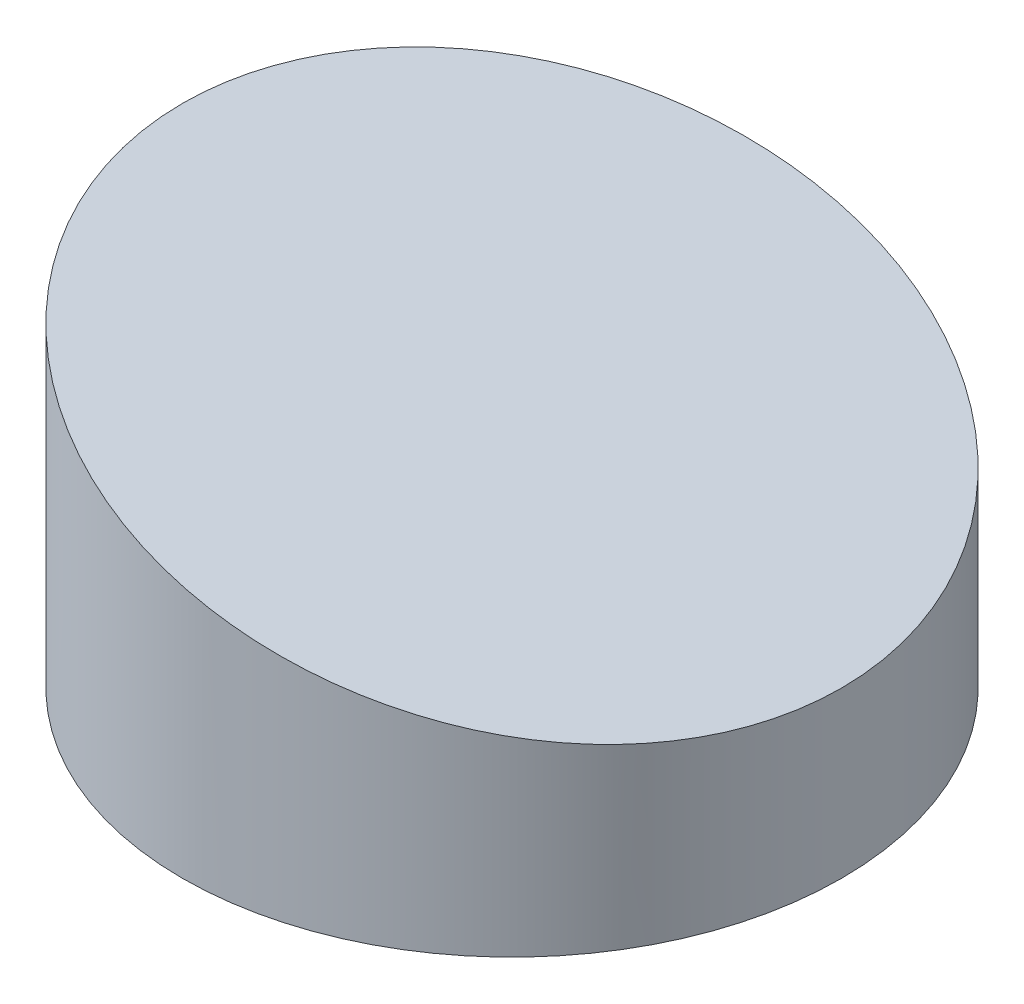
SolidWorks part; units mm, degrees
material "6061-T4 (SS)"
ref_plane "Front Plane" through (0, 0, 0) normal (0, 0, 1) x (1, 0, 0)
ref_plane "Top Plane" through (0, 0, 0) normal (0, 1, 0) x (1, 0, 0)
ref_plane "Right Plane" through (0, 0, 0) normal (1, 0, 0) x (0, 0, -1)
sketch "Sketch1" plane through (0, 0, 0) normal (0, 1, 0) x (1, 0, 0)
  circle A0 centre (0, 0) radius 12.7
  dimension "D1" = 25.4
extrude "Boss-Extrude1" add sketch "Sketch1" along normal blind 13.16
sketch "Sketch2" plane through (0, 0, 0) normal (0, 0, 1) x (1, 0, 0)
  line L0 (-12.7, 13.16) -> (12.7, 6.35)
  line L1 (12.7, 0) -> (12.7, 13.16) construction
  dimension "D1" = 6.35
extrude "Cut-Extrude4" cut sketch "Sketch2" against normal through all and the other way through all contours L0
sketch "Sketch4" plane through (0, 0, 0) normal (0, 1, 0) x (1, 0, 0)
  line L0 (-12.7, 0) -> (12.7, 0)
  circle A1 centre (0, 0) radius 12.7 construction
  circle A2 centre (-9.525, 0) radius 1.595
  circle A3 centre (0, 0) radius 9.525
  circle A4 centre (0.005, 0) radius 1.595
  circle A5 centre (9.535, 0) radius 1.595
  circle A7 centre (4.7625, 8.2489) radius 1.595
  circle A8 centre (4.7625, -8.2489) radius 1.595
  point P2 (9.4877, 0)
  point P8 (-9.525, 0)
  point P21 (0, 0)
  dimension "D1" = 19.05
  dimension "D2" = 3.19
  dimension "D3" = 3
  dimension "D4" = 3
extrude "Cut-Extrude9" cut sketch "Sketch4" along normal blind 4.32 contours A8 | A5 | A7 | A4 | A2
